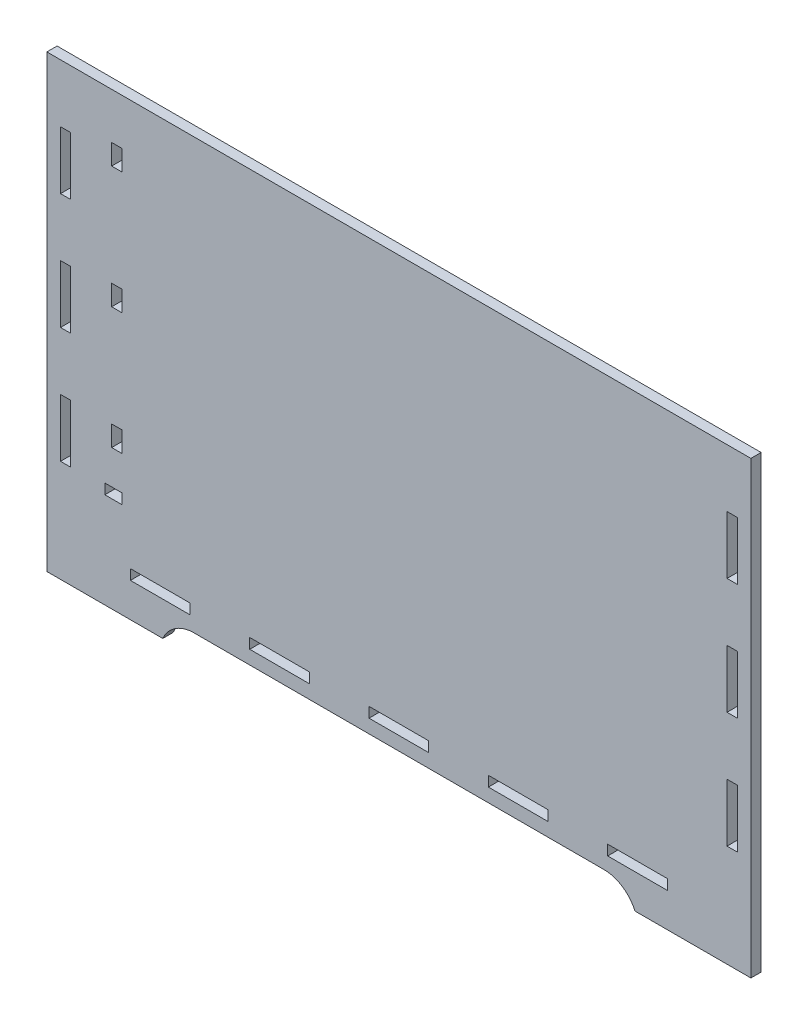
SolidWorks part; units mm, degrees
ref_plane "Front Plane" through (0, 0, 0) normal (0, 0, 1) x (1, 0, 0)
ref_plane "Top Plane" through (0, 0, 0) normal (0, 1, 0) x (1, 0, 0)
ref_plane "Right Plane" through (0, 0, 0) normal (1, 0, 0) x (0, 0, -1)
sketch "Sketch1" plane through (0, 0, 0) normal (0, 0, 1) x (1, 0, 0)
  line L1 (-192.5, -119) -> (192.5, -119)
  line L2 (-192.5, -119) -> (-192.5, 119)
  line L3 (-192.5, 119) -> (192.5, 119)
  line L4 (192.5, -119) -> (192.5, 119)
  line L5 (-192.5, -119) -> (192.5, 119) construction
  line L6 (-192.5, 119) -> (192.5, -119) construction
  point P0 (0, 0)
  dimension "D1" = 385
  dimension "D2" = 238
extrude "Boss-Extrude1" add sketch "Sketch1" along normal blind 6 contours L2 L3 L4 L1
sketch "Sketch2" plane through (0, 0, 0) normal (0, 0, -1) x (-1, 0, 0)
  line L1 (162.5, 92) -> (168.5, 92)
  line L2 (162.5, 92) -> (162.5, 80)
  line L3 (162.5, 80) -> (168.5, 80)
  line L4 (168.5, 92) -> (168.5, 80)
  line L5 (162.5, 20.5) -> (168.5, 20.5)
  line L6 (162.5, 20.5) -> (162.5, 8.5)
  line L7 (162.5, 8.5) -> (168.5, 8.5)
  line L8 (168.5, 20.5) -> (168.5, 8.5)
  line L9 (162.5, -51) -> (168.5, -51)
  line L10 (162.5, -51) -> (162.5, -63)
  line L11 (162.5, -63) -> (168.5, -63)
  line L12 (168.5, -51) -> (168.5, -63)
  line L13 (162.5, -83) -> (172.5, -83)
  line L14 (162.5, -83) -> (162.5, -89)
  line L15 (162.5, -89) -> (172.5, -89)
  line L16 (172.5, -83) -> (172.5, -89)
extrude "Cut-Extrude1" cut sketch "Sketch2" against normal blind 6
sketch "Sketch3" plane through (-192.5, 0, 0) normal (-1, 0, 0) x (0, 0, 1)
  line L0 (0, -119) -> (0, 119) construction
  line L1 (6, 119) -> (0, 119)
  line L2 (6, 119) -> (6, 85)
  line L3 (6, 85) -> (0, 85)
  line L4 (0, 119) -> (0, 85)
  line L5 (6, -119) -> (6, 119) construction
  line L6 (0, 85) -> (6, 85)
  line L7 (0, 85) -> (0, 51)
  line L8 (0, 51) -> (6, 51)
  line L9 (6, 85) -> (6, 51)
  line L11 (6, 51) -> (0, 51)
  line L12 (6, 51) -> (6, 17)
  line L13 (6, 17) -> (0, 17)
  line L14 (0, 51) -> (0, 17)
  line L15 (0, 17) -> (6, 17)
  line L16 (0, 17) -> (0, -17)
  line L17 (0, -17) -> (6, -17)
  line L18 (6, 17) -> (6, -17)
  line L19 (6, -17) -> (0, -17)
  line L20 (6, -17) -> (6, -51)
  line L21 (6, -51) -> (0, -51)
  line L22 (0, -17) -> (0, -51)
  line L23 (0, -51) -> (6, -51)
  line L24 (0, -51) -> (0, -85)
  line L25 (0, -85) -> (6, -85)
  line L26 (6, -51) -> (6, -85)
  line L27 (6, -85) -> (0, -85)
  line L28 (6, -85) -> (6, -119)
  line L29 (6, -119) -> (0, -119)
  line L30 (0, -85) -> (0, -119)
  line M17 (0, 119) -> (0, -119)
  line M18 (0, -119) -> (6, -119)
  line M19 (6, -119) -> (6, 119)
  line M20 (6, 119) -> (0, 119)
extrude "Boss-Extrude2" add sketch "Sketch3" along normal blind 6 contours L3 M19 M20 M17 | L13 L8 M19 M17 | L21 L17 M19 M17 | L25 M17 M18 M19 region at (-192.5, 102, 3) region at (-192.5, 34, 3) region at (-192.5, -34, 3) region at (-192.5, -102, 3)
mirror "Mirror1" about plane through (0, 0, 0) normal (1, 0, 0) of "Boss-Extrude2"
sketch "Sketch4" plane through (0, -119, 0) normal (0, -1, 0) x (1, 0, 0)
  line L0 (-198.5, 6) -> (198.5, 6) construction
  line L1 (-192.5, 0) -> (-157.5, 0)
  line L2 (-192.5, 0) -> (-192.5, 6)
  line L3 (-192.5, 6) -> (-157.5, 6)
  line L4 (-157.5, 0) -> (-157.5, 6)
  line L5 (-198.5, 0) -> (198.5, 0) construction
  line L7 (-157.5, 6) -> (-157.5, 0)
  line L9 (-157.5, 6) -> (-157.5, 0)
  line L11 (-157.5, 0) -> (-122.5, 0)
  line L12 (-157.5, 0) -> (-157.5, 6)
  line L13 (-157.5, 6) -> (-122.5, 6)
  line L14 (-122.5, 0) -> (-122.5, 6)
  line L15 (-122.5, 6) -> (-87.5, 6)
  line L16 (-122.5, 6) -> (-122.5, 0)
  line L17 (-122.5, 0) -> (-87.5, 0)
  line L18 (-87.5, 6) -> (-87.5, 0)
  line L19 (-87.5, 0) -> (-52.5, 0)
  line L20 (-87.5, 0) -> (-87.5, 6)
  line L21 (-87.5, 6) -> (-52.5, 6)
  line L22 (-52.5, 0) -> (-52.5, 6)
  line L23 (-52.5, 6) -> (-17.5, 6)
  line L24 (-52.5, 6) -> (-52.5, 0)
  line L25 (-52.5, 0) -> (-17.5, 0)
  line L26 (-17.5, 6) -> (-17.5, 0)
  line L27 (-17.5, 0) -> (17.5, 0)
  line L28 (-17.5, 0) -> (-17.5, 6)
  line L29 (-17.5, 6) -> (17.5, 6)
  line L30 (17.5, 0) -> (17.5, 6)
  line L31 (17.5, 6) -> (52.5, 6)
  line L32 (17.5, 6) -> (17.5, 0)
  line L33 (17.5, 0) -> (52.5, 0)
  line L34 (52.5, 6) -> (52.5, 0)
  line L35 (52.5, 0) -> (87.5, 0)
  line L36 (52.5, 0) -> (52.5, 6)
  line L37 (52.5, 6) -> (87.5, 6)
  line L38 (87.5, 0) -> (87.5, 6)
  line L39 (87.5, 6) -> (122.5, 6)
  line L40 (87.5, 6) -> (87.5, 0)
  line L41 (87.5, 0) -> (122.5, 0)
  line L42 (122.5, 6) -> (122.5, 0)
  line L43 (122.5, 0) -> (157.5, 0)
  line L44 (122.5, 0) -> (122.5, 6)
  line L45 (122.5, 6) -> (157.5, 6)
  line L46 (157.5, 0) -> (157.5, 6)
  line L47 (157.5, 6) -> (192.5, 6)
  line L48 (157.5, 6) -> (157.5, 0)
  line L49 (157.5, 0) -> (192.5, 0)
  line L50 (192.5, 6) -> (192.5, 0)
  line L51 (192.5, 0) -> (198.5, 0)
  line L52 (192.5, 0) -> (192.5, 6)
  line L53 (192.5, 6) -> (198.5, 6)
  line L54 (198.5, 0) -> (198.5, 6)
  line L55 (-192.5, 0) -> (-198.5, 0)
  line L56 (-192.5, 0) -> (-192.5, 6)
  line L57 (-192.5, 6) -> (-198.5, 6)
  line L58 (-198.5, 0) -> (-198.5, 6)
  point P33 (-189.6199, 0)
  point P35 (-148.6947, 0)
  point P36 (0, 0)
  line M42 (-198.5, 0) -> (198.5, 0)
  line M43 (198.5, 0) -> (198.5, 6)
  line M44 (198.5, 6) -> (-198.5, 6)
  line M45 (-198.5, 6) -> (-198.5, 0)
  dimension "D1" = 6
extrude "Boss-Extrude3" add sketch "Sketch4" along normal blind 6 contours L4 L2 M42 M44 | L2 M42 M44 M45 | L18 L14 M44 M42 | L26 L22 M44 M42 | L34 L30 M44 M42 | L42 L38 M44 M42 | L50 L46 M44 M42 | L50 M44 M42 M43 region at (-175, -119, 3) region at (-195.5, -119, 3) region at (-105, -119, 3) region at (-35, -119, 3) region at (35, -119, 3) region at (105, -119, 3) region at (175, -119, 3) region at (195.5, -119, 3)
sketch "Sketch5" plane through (0, 0, 0) normal (0, 0, -1) x (-1, 0, 0)
  line L1 (198.5, -125) -> (-198.5, -125)
  line L2 (198.5, -125) -> (198.5, -133)
  line L3 (198.5, -133) -> (-198.5, -133)
  line L4 (-198.5, -125) -> (-198.5, -133)
  line L5 (-198.5, -133) -> (-138.5, -133)
  line L6 (-198.5, -133) -> (-198.5, -145)
  line L7 (-198.5, -145) -> (-138.5, -145)
  line L8 (-138.5, -133) -> (-138.5, -145)
  line L9 (198.5, -133) -> (138.5, -133)
  line L10 (198.5, -133) -> (198.5, -145)
  line L11 (198.5, -145) -> (138.5, -145)
  line L12 (138.5, -133) -> (138.5, -145)
  point P17 (0, 0)
  point P18 (-79.4126, -133)
  point P23 (0, 0)
  point P25 (0, 0)
  dimension "D1" = 8
  dimension "D2" = 12
  dimension "D3" = 60
extrude "Boss-Extrude4" add sketch "Sketch5" against normal blind 6 contours L3 L12 L11 L10 | L8 L3 L6 L7 | L1 L4 L3 L2 region at (0, -129, 0) region at (-168.5, -139, 0) region at (168.5, -139, 0)
fillet "Fillet1" radius 20 2 edges at (138.5, -133, 3) (-138.5, -133, 3)
sketch "Sketch6" plane through (-198.5, 0, 0) normal (-1, 0, 0) x (0, 0, 1)
  line L1 (0, -145) -> (6, -145)
  line L2 (0, -145) -> (0, 119)
  line L3 (0, 119) -> (6, 119)
  line L4 (6, -145) -> (6, 119)
extrude "Boss-Extrude5" add sketch "Sketch6" along normal blind 8
mirror "Mirror2" about plane through (0, 0, 0) normal (1, 0, 0) of "Boss-Extrude5"
